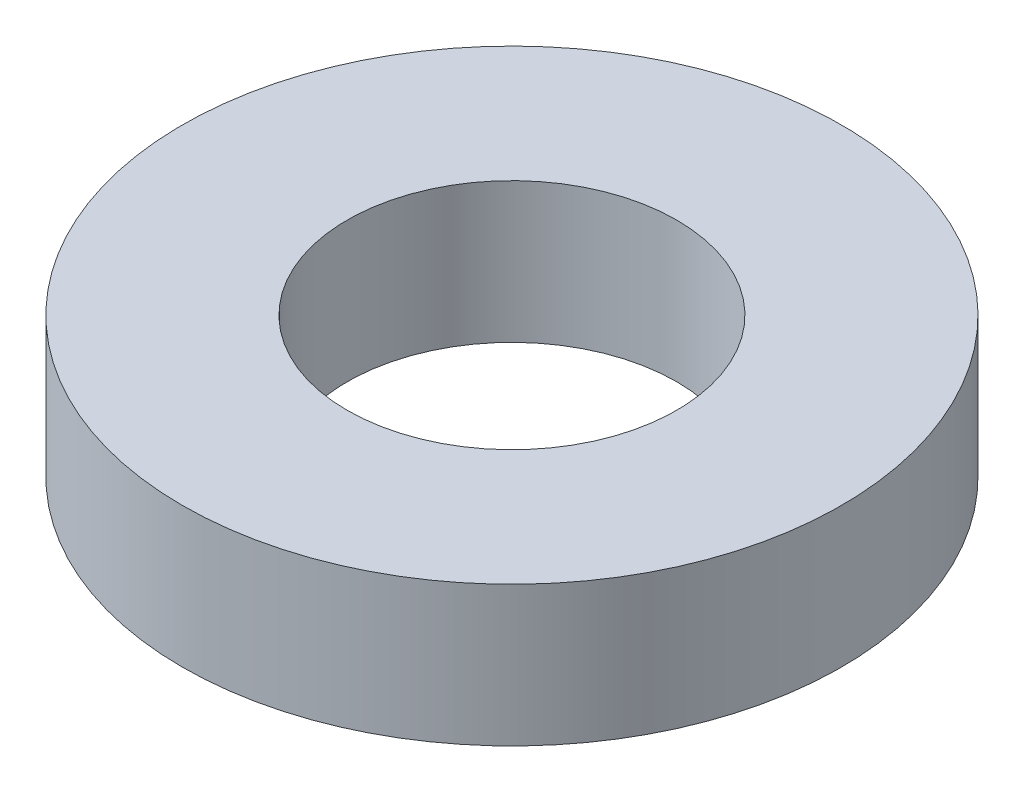
SolidWorks part; units mm, degrees
ref_plane "Front Plane" through (0, 0, 0) normal (0, 0, 1) x (1, 0, 0)
ref_plane "Top Plane" through (0, 0, 0) normal (0, 1, 0) x (1, 0, 0)
ref_plane "Right Plane" through (0, 0, 0) normal (1, 0, 0) x (0, 0, -1)
sketch "Sketch1" plane through (0, 0, 0) normal (0, 1, 0) x (1, 0, 0)
  circle A0 centre (0, 0) radius 40
  dimension "FLANGE_OD" = 80
extrude "Boss-Extrude1" add sketch "Sketch1" along normal blind 17
sketch "Sketch2" plane through (0, 0, 0) normal (0, 1, 0) x (1, 0, 0)
  circle A0 centre (0, 0) radius 20
  dimension "BORE_D" = 40
extrude "Cut-Extrude1" cut sketch "Sketch2" along normal through all
sketch "Sketch3" plane through (0, 17, 0) normal (0, 1, 0) x (1, 0, 0)
  circle A0 centre (0, 0) radius 12.0108 construction
  circle A1 centre (-12.0108, 0) radius 2.5006
  dimension "BOLT_D" = 5.0013
  dimension "BOLT_PCD" = 24.0216
extrude "Cut-Extrude2" cut sketch "Sketch3" against normal blind 12.3818 rebuild error yes
pattern_circular "CirPattern1" count 3 over 360 rebuild error yes
